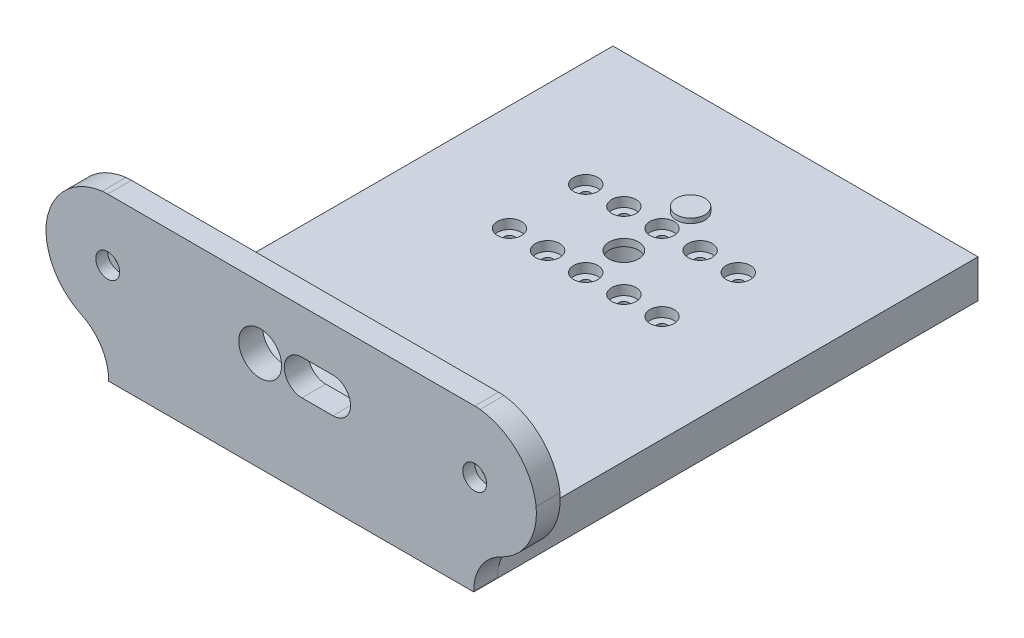
SolidWorks part; units mm, degrees
ref_plane "正面" through (0, 0, 0) normal (0, 0, 1) x (1, 0, 0)
ref_plane "平面" through (0, 0, 0) normal (0, 1, 0) x (1, 0, 0)
ref_plane "右側面" through (0, 0, 0) normal (1, 0, 0) x (0, 0, -1)
sketch "ｽｹｯﾁ1" plane through (0, 0, 0) normal (0, 1, 0) x (1, 0, 0)
  line L0 (0, 50.4) -> (0, 0) construction
  line L1 (-38.3, 50.4) -> (38.3, 50.4)
  line L2 (-38.3, 50.4) -> (-38.3, -50.4)
  line L3 (-38.3, -50.4) -> (38.3, -50.4)
  line L4 (38.3, 50.4) -> (38.3, -50.4)
  line L5 (-38.3, 50.4) -> (38.3, -50.4) construction
  line L6 (-38.3, -50.4) -> (38.3, 50.4) construction
  circle A0 centre (0, 14.4) radius 3.1
  point P0 (0, 0)
  dimension "D3" = 6.2
  dimension "D1" = 76.6
  dimension "D2" = 100.8
  dimension "D4" = 36
extrude "ﾎﾞｽ - 押し出し1" add sketch "ｽｹｯﾁ1" along normal blind 8
sketch "ｽｹｯﾁ2" plane through (0, 0, 0) normal (0, -1, 0) x (1, 0, 0)
  circle A0 centre (0, -14.4) radius 3.1 construction
  circle A1 centre (0, -14.4) radius 3.1 construction
  circle A2 centre (0, -14.4) radius 5.25
  dimension "D1" = 10.5
extrude "ｶｯﾄ - 押し出し1" cut sketch "ｽｹｯﾁ2" against normal blind 6.5
sketch "ｽｹｯﾁ3" plane through (0, 8, 0) normal (0, 1, 0) x (1, 0, 0)
  line L0 (0, 50.4) -> (0, 0) construction
  line L1 (38.3, 50.4) -> (-38.3, 50.4) construction
  circle A0 centre (0, 28.4) radius 3
  dimension "D1" = 6
  dimension "D2" = 22
extrude "ﾎﾞｽ - 押し出し2" add sketch "ｽｹｯﾁ3" along normal blind 1
sketch "ｽｹｯﾁ5" plane through (0, 8, 0) normal (0, 1, 0) x (1, 0, 0)
  line L0 (-38.3, 14.4) -> (38.3, 14.4) construction
  line L1 (-38.3, 50.4) -> (-38.3, -50.4) construction
  line L2 (38.3, -50.4) -> (38.3, 50.4) construction
  line L3 (0, 50.4) -> (0, -50.4) construction
  line L4 (38.3, 50.4) -> (-38.3, 50.4) construction
  line L5 (-38.3, -50.4) -> (38.3, -50.4) construction
  circle A0 centre (0, 14.4) radius 3.1 construction
  circle A1 centre (0, 22.4) radius 1.05
  circle A2 centre (8, 22.4) radius 1.05
  circle A3 centre (16, 22.4) radius 1.05
  circle A4 centre (-8, 22.4) radius 1.05
  circle A5 centre (-16, 22.4) radius 1.05
  circle A6 centre (-16, 6.4) radius 1.05
  circle A7 centre (-8, 6.4) radius 1.05
  circle A8 centre (16, 6.4) radius 1.05
  circle A9 centre (8, 6.4) radius 1.05
  circle A10 centre (0, 6.4) radius 1.05
  point P12 (0, 14.4)
  dimension "D1" = 2.1
  dimension "D2" = 8
  dimension "D3" = 3
  dimension "D4" = 3
extrude "ｶｯﾄ - 押し出し2" cut sketch "ｽｹｯﾁ5" against normal through all
sketch "ｽｹｯﾁ6" plane through (0, 8, 0) normal (0, 1, 0) x (1, 0, 0)
  circle A86 centre (-8, 22.4) radius 2.55
  circle A87 centre (-16, 22.4) radius 2.55
  circle A88 centre (-16, 22.4) radius 2.55
  circle A89 centre (0, 22.4) radius 2.55
  circle A90 centre (8, 22.4) radius 2.55
  circle A91 centre (16, 22.4) radius 2.55
  circle A92 centre (-8, 6.4) radius 2.55
  circle A93 centre (0, 6.4) radius 2.55
  circle A94 centre (8, 6.4) radius 2.55
  circle A95 centre (16, 6.4) radius 2.55
  circle A96 centre (-16, 6.4) radius 2.55
  dimension "D1" = 1.5
  dimension "D2" = 5
  dimension "D3" = 2
extrude "ｶｯﾄ - 押し出し3" cut sketch "ｽｹｯﾁ6" against normal blind 2
sketch "ｽｹｯﾁ7" plane through (0, 0, 50.4) normal (0, 0, 1) x (1, 0, 0)
  line L4 (-38.3, 0) -> (38.3, 0)
  line L5 (38.3, 0) -> (38.3, 8)
  line L6 (38.3, 8) -> (-38.3, 8)
  line L7 (-38.3, 8) -> (-38.3, 0)
  line L8 (-38.3, 0) -> (38.3, 0)
  line L12 (38.3, 8) -> (38.5, 8)
  line L13 (-38.3, 8) -> (-38.5, 8)
  line L14 (-38.5, 33.9) -> (38.5, 33.9) construction
  line L21 (38.3, 8) -> (38.3, 0) construction
  line L22 (-38.3, 8) -> (-38.3, 0) construction
  line L23 (-38.5, 33.9) -> (38.5, 33.9)
  line L24 (38.3, 8) -> (38.3, 0)
  line L25 (-38.3, 8) -> (-38.3, 0)
  line L26 (8.75, 24.65) -> (2.25, 24.65)
  line L27 (2.25, 17.25) -> (8.75, 17.25)
  line L28 (8.75, 24.65) -> (2.25, 24.65)
  line L33 (2.25, 17.25) -> (8.75, 17.25)
  arc A0 (39.6485, 33.849) -> (38.5, 33.9) centre (38.5, 20.95) ccw construction
  arc A1 (-38.5, 33.9) -> (-39.6485, 33.849) centre (-38.5, 20.95) ccw construction
  circle A2 centre (-38.5, 20.95) radius 1.125
  arc A4 (39.6485, 33.849) -> (38.5, 33.9) centre (38.5, 20.95) ccw
  arc A5 (-38.5, 33.9) -> (-39.6485, 33.849) centre (-38.5, 20.95) ccw
  circle A17 centre (-38.5, 20.95) radius 1.125
  arc A23 (-51.399, 22.0985) -> (-38.5, 8) centre (-38.5, 20.95) ccw construction
  arc A24 (-39.6485, 33.849) -> (-51.399, 22.0985) centre (-38, 20.45) ccw construction
  arc A25 (51.399, 22.0985) -> (39.6485, 33.849) centre (38, 20.45) ccw construction
  arc A26 (38.5, 8) -> (51.399, 22.0985) centre (38.5, 20.95) ccw construction
  arc A27 (-51.399, 22.0985) -> (-38.5, 8) centre (-38.5, 20.95) ccw
  arc A28 (-39.6485, 33.849) -> (-51.399, 22.0985) centre (-38, 20.45) ccw
  arc A29 (51.399, 22.0985) -> (39.6485, 33.849) centre (38, 20.45) ccw
  arc A30 (38.5, 8) -> (51.399, 22.0985) centre (38.5, 20.95) ccw
  circle A43 centre (-6.5, 20.95) radius 4.5
  circle A44 centre (-6.5, 20.95) radius 4.5
  arc A51 (8.75, 17.25) -> (8.75, 24.65) centre (8.75, 20.95) ccw
  arc A52 (2.25, 24.65) -> (2.25, 17.25) centre (2.25, 20.95) ccw
  arc A53 (8.75, 17.25) -> (8.75, 24.65) centre (8.75, 20.95) ccw
  arc A54 (2.25, 24.65) -> (2.25, 17.25) centre (2.25, 20.95) ccw
  circle A55 centre (38.5, 20.95) radius 1.125
  circle A56 centre (38.5, 20.95) radius 1.125
  dimension "D1" = 0
  dimension "D3" = 0.1
  dimension "D4" = 2
  dimension "D5" = 2
  dimension "D6" = 0.1
extrude "ﾎﾞｽ - 押し出し3" add sketch "ｽｹｯﾁ7" along normal blind 5
fillet "ﾌｨﾚｯﾄ1" radius 10 2 edges at (-38.3, 8, 52.9) (38.3, 8, 52.9)
sketch "ｽｹｯﾁ8" plane through (0, 0, 55.4) normal (0, 0, 1) x (1, 0, 0)
  circle A0 centre (-38.5, 20.95) radius 2.5
  circle A1 centre (38.5, 20.95) radius 2.5
  dimension "D1" = 5
extrude "ｶｯﾄ - 押し出し4" cut sketch "ｽｹｯﾁ8" against normal blind 2.5
